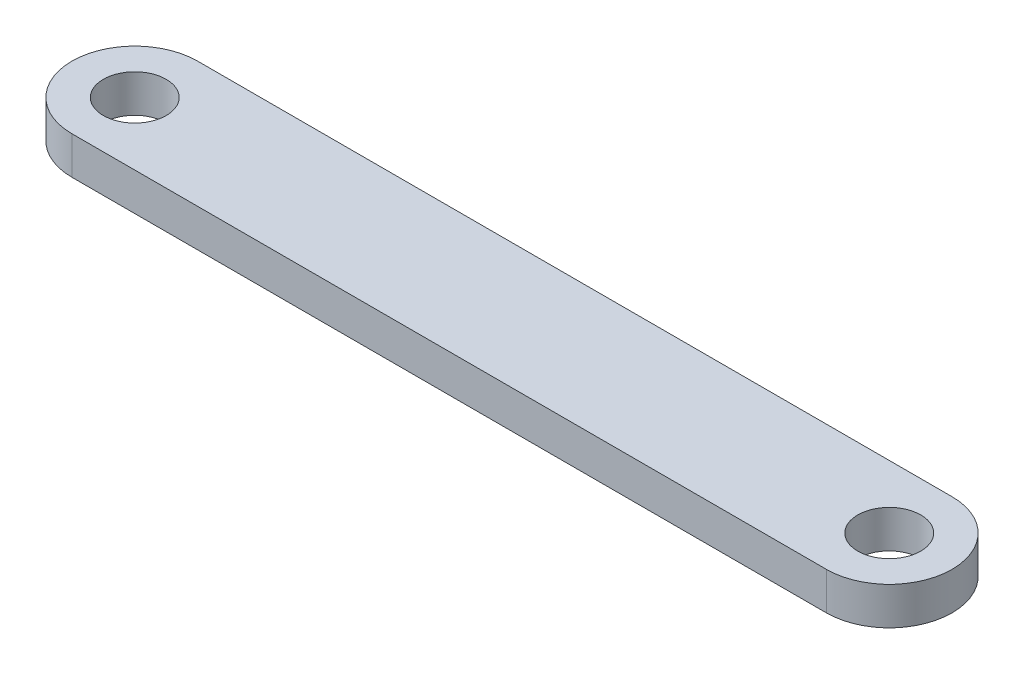
SolidWorks part; units mm, degrees
ref_plane "Front Plane" through (0, 0, 0) normal (0, 0, 1) x (1, 0, 0)
ref_plane "Top Plane" through (0, 0, 0) normal (0, 1, 0) x (1, 0, 0)
ref_plane "Right Plane" through (0, 0, 0) normal (1, 0, 0) x (0, 0, -1)
sketch "Sketch1" plane through (0, 0, 0) normal (0, 1, 0) x (1, 0, 0)
  line L0 (-38.1, 0) -> (38.1, 0) construction
  line L1 (-38.1, 6.35) -> (38.1, 6.35)
  line L2 (-38.1, -6.35) -> (38.1, -6.35)
  arc A0 (-38.1, 6.35) -> (-38.1, -6.35) centre (-38.1, 0) ccw
  arc A1 (38.1, -6.35) -> (38.1, 6.35) centre (38.1, 0) ccw
  circle A2 centre (-38.1, 0) radius 3.175
  circle A3 centre (38.1, 0) radius 3.175
  point P3 (0, 0)
  dimension "D2" = 6.35
  dimension "D3" = 6.35
  dimension "D4" = 6.35
  dimension "D1" = 76.2
extrude "Boss-Extrude1" add sketch "Sketch1" along normal blind 3.81
